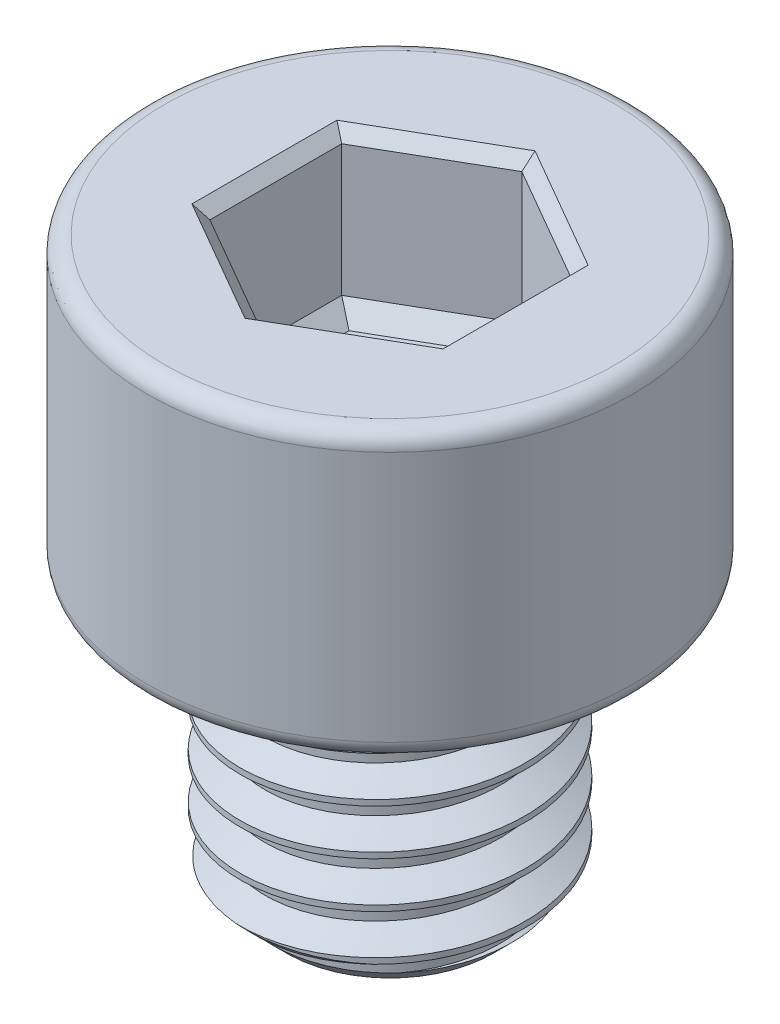
SolidWorks part; units mm, degrees
material "AISI Type A2 Tool Steel"
ref_plane "Front Plane" through (0, 0, 0) normal (0, 0, 1) x (1, 0, 0)
ref_plane "Top Plane" through (0, 0, 0) normal (0, 1, 0) x (1, 0, 0)
ref_plane "Right Plane" through (0, 0, 0) normal (1, 0, 0) x (0, 0, -1)
sketch "Sketch1" plane through (0, 0, 0) normal (0, 1, 0) x (1, 0, 0)
  circle A0 centre (0, 0) radius 2.5
  dimension "D1" = 5
extrude "Boss-Extrude1" add sketch "Sketch1" along normal blind 5
thread "Thread1" pitch 0.8 method cut profile "Thread Profile1" start angle 0, offset 1, length 0, pitch 0.8, diameter 5
ref_plane "Plane1" through (-2.5, 6, 0) normal (0, 0, 1) x (-1, 0, 0)
sketch "Thread Profile1" plane through (-2.5, 6, 0) normal (0, 0, 1) x (-1, 0, 0)
  line L0 (0, 0) -> (0, 0.8) construction
  line L11 (0, 0) -> (0, 0.7)
  line L12 (0, 0.7) -> (-0.433, 0.45)
  line L13 (-0.433, 0.45) -> (-0.433, 0.25)
  line L15 (-0.433, 0.25) -> (0, 0)
  line L17 (-0.433, 0.35) -> (0, 0.35) construction
  point P2 (0, 0)
  dimension "Pitch" = 0.8
  dimension "Profile_Angle" = 60
  dimension "Profile_Land" = 0.2
  dimension "Profile_Height" = 0.433
sketch "Sketch5" plane through (0, 5, 0) normal (0, 1, 0) x (1, 0, 0)
  circle A0 centre (0, 0) radius 4.25
  dimension "D1" = 8.5
extrude "Boss-Extrude2" add sketch "Sketch5" along normal blind 5
fillet "Fillet1" radius 0.3 2 edges at (0, 5, 4.25) (0, 10, 4.25)
sketch "Sketch6" plane through (0, 0, 0) normal (0, 0, 1) x (1, 0, 0)
  line L0 (0, 0) -> (0, 0.2882) construction
  line L1 (0, 0) -> (2.51, 0) construction
  line L2 (2.51, 0) -> (2.51, 0.7)
  line L3 (2.51, 0.7) -> (1.81, 0)
  line L4 (1.81, 0) -> (2.51, 0)
  dimension "D1" = 45
  dimension "D2" = 0.7
  dimension "D3" = 2.51
revolve "Cut-Revolve1" cut sketch "Sketch6" angle 360 about L0
sketch "Sketch7" plane through (0, 10, 0) normal (0, 1, 0) x (1, 0, 0)
  line L1 (0, 2.3094) -> (-2, 1.1547)
  line L2 (-2, 1.1547) -> (-2, -1.1547)
  line L3 (-2, -1.1547) -> (0, -2.3094)
  line L4 (0, -2.3094) -> (2, -1.1547)
  line L5 (2, -1.1547) -> (2, 1.1547)
  line L6 (2, 1.1547) -> (0, 2.3094)
  circle A0 centre (0, 0) radius 2 construction
  dimension "D1" = 4
extrude "Cut-Extrude1" cut sketch "Sketch7" against normal blind 2.5
chamfer "Chamfer1" distance 0.2 angle 45 6 edges at (-2, 10, 0) (-1, 10, 1.7321) (1, 10, 1.7321) (2, 10, 0) (1, 10, -1.7321) (-1, 10, -1.7321)
sketch "Sketch8" plane through (0, 7.5, 0) normal (0, 1, 0) x (1, 0, 0)
  line L1 (0, 2.3094) -> (-2, 1.1547)
  line L2 (-2, 1.1547) -> (-2, -1.1547)
  line L3 (-2, -1.1547) -> (0, -2.3094)
  line L4 (0, -2.3094) -> (2, -1.1547)
  line L5 (2, -1.1547) -> (2, 1.1547)
  line L6 (2, 1.1547) -> (0, 2.3094)
  circle A0 centre (0, 0) radius 2 construction
extrude "Cut-Extrude2" cut sketch "Sketch8" against normal blind 0.3 draft 45
